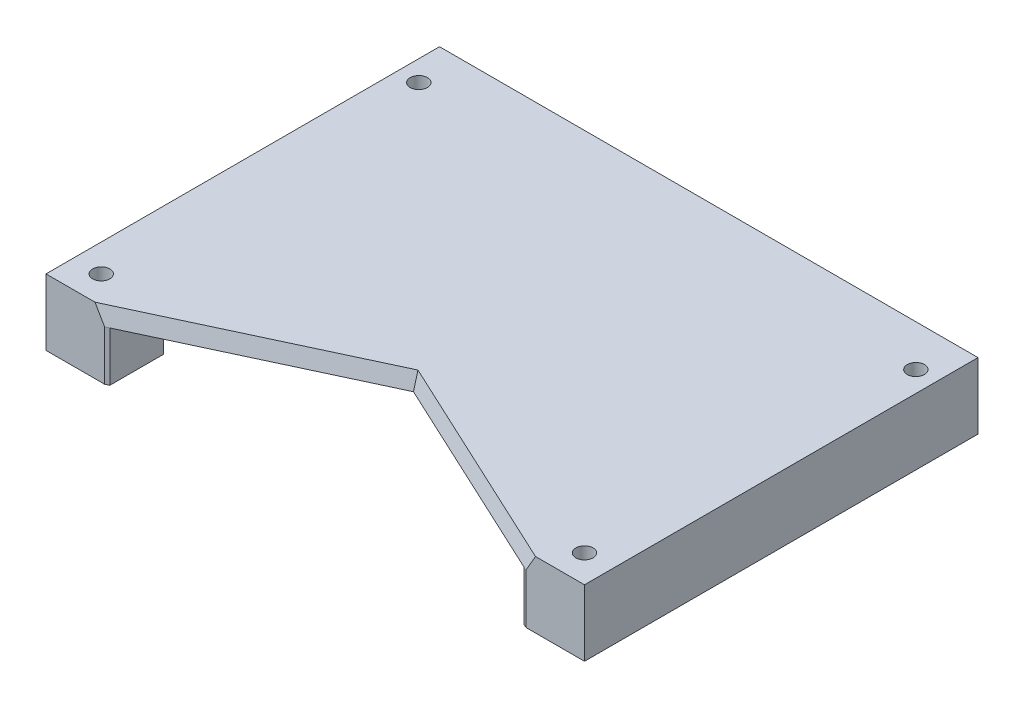
SolidWorks part; units mm, degrees
ref_plane "Front Plane" through (0, 0, 0) normal (0, 0, 1) x (1, 0, 0)
ref_plane "Top Plane" through (0, 0, 0) normal (0, 1, 0) x (1, 0, 0)
ref_plane "Right Plane" through (0, 0, 0) normal (1, 0, 0) x (0, 0, -1)
sketch "Sketch1" plane through (0, 0, 0) normal (0, 1, 0) x (1, 0, 0)
  line L1 (0, 0) -> (78, 0)
  line L2 (0, 0) -> (0, 57)
  line L3 (0, 57) -> (78, 57)
  line L4 (78, 0) -> (78, 57)
  dimension "D1" = 57
  dimension "D2" = 78
extrude "Boss-Extrude1" add sketch "Sketch1" along normal blind 9.6
sketch "Sketch2" plane through (0, 0, 0) normal (0, -1, 0) x (1, 0, 0)
  line L0 (78, -57) -> (0, -57) construction
  line L1 (6, -57) -> (72, -57)
  line L2 (6, -57) -> (6, -8)
  line L3 (6, -8) -> (72, -8)
  line L4 (72, -57) -> (72, -8)
  line L5 (0, -57) -> (0, 0) construction
  line L6 (78, 0) -> (78, -57) construction
  dimension "D1" = 6
  dimension "D2" = 6
  dimension "D3" = 49
extrude "Cut-Extrude1" cut sketch "Sketch2" against normal blind 7.2
sketch "Sketch3" plane through (0, 0, 0) normal (0, -1, 0) x (1, 0, 0)
  line L0 (72, -8) -> (6, -8) construction
  line L1 (9, -8) -> (69, -8)
  line L2 (9, -8) -> (9, 0)
  line L3 (9, 0) -> (69, 0)
  line L4 (69, -8) -> (69, 0)
  line L5 (0, 0) -> (78, 0) construction
  line L6 (0, -57) -> (0, 0) construction
  line L7 (78, 0) -> (78, -57) construction
  dimension "D1" = 9
  dimension "D2" = 9
extrude "Cut-Extrude2" cut sketch "Sketch3" against normal up to surface (7.2 mm away) up to face at (39, 7.2, -32.5)
sketch "Sketch4" plane through (0, 9.6, 0) normal (0, 1, 0) x (1, 0, 0)
  line L0 (0, 0) -> (78, 0) construction
  line L1 (6, 0) -> (39, 15.3882)
  line L2 (39, 15.3882) -> (72, 0)
  line L3 (39, 15.3882) -> (39, 57) construction
  line L4 (72, 0) -> (6, 0)
  line L5 (78, 57) -> (0, 57) construction
  dimension "D1" = 130
  dimension "D2" = 6
extrude "Cut-Extrude3" cut sketch "Sketch4" against normal up to next
hole_wizard "Tap Drill for M3 Tap1" positions "Sketch6" profile "Sketch5" hole size "M3" standard "ISO" end condition up to next
sketch "Sketch6" plane through (0, 0, 0) normal (0, -1, 0) x (-1, 0, 0)
  line L0 (-78, 57) -> (-72, 57) construction
  line L1 (-6, 57) -> (0, 57) construction
  line L2 (-72, 0) -> (-78, 0) construction
  line L3 (-78, 0) -> (-78, 57) construction
  line L5 (0, 57) -> (0, 0) construction
  point P0 (-4, 4)
  point P2 (-3, 51)
  point P4 (-74, 4)
  point P6 (-75, 51)
  dimension "D1" = 6
  dimension "D2" = 6
  dimension "D3" = 4
  dimension "D4" = 4
  dimension "D5" = 4
  dimension "D6" = 3
  dimension "D7" = 3
sketch "Sketch5" plane through (4, 0, -4) normal (1, 0, 0) x (0, 0, -1)
  line L0 (0, 0) -> (0, 9.6)
  line L1 (0, 9.6) -> (1.25, 9.6)
  line L2 (1.25, 9.6) -> (1.25, 0)
  line L5 (1.25, 0) -> (0, 0)
  line L11 (0, -6.35) -> (0, 107.95) construction
  dimension "Thru Hole Dia." = 2.5
  dimension "Thru Hole Depth" = 9.6
ref_plane "Plane1" through (59.1404, 0, 27.5776) normal (0.9063, 0, 0.4226) x (0, 1, 0)
sketch "Sketch7" plane through (0, 9.6, 0) normal (0, 1, 0) x (1, 0, 0)
  line L0 (6, 0) -> (10.7324, 0)
  line L1 (10.7324, 0) -> (39, 13.1814)
  line L2 (39, 13.1814) -> (67.2676, 0)
  line L3 (67.2676, 0) -> (72, 0)
  line L4 (72, 0) -> (39, 15.3882)
  line L5 (39, 15.3882) -> (6, 0)
  dimension "D1" = 2
extrude "Boss-Extrude2" add sketch "Sketch7" against normal up to surface (2.4 mm away) up to face at (39, 7.2, -18.2429)
sketch "Sketch8" plane through (59.1404, 0, 27.5776) normal (0.9063, 0, 0.4226) x (0, 1, 0)
  line L0 (-8, 1.5251) -> (-8, -29.9285) construction
  line L1 (9.6, -29.9285) -> (-8, -29.9285) construction
  line L2 (9.6, -32.9642) -> (9.6, -84.6238) construction
  line L3 (7.2, -9.7862) -> (7.2, -54.1953) construction
  line L4 (9.6, -28.4285) -> (9.6, -32.9642) construction
  line L5 (7.2, -29.378) -> (9.6, -29.9651)
  line L6 (9.6, -29.9651) -> (9.6, -29.7223) construction
  line L7 (7.2, -29.378) -> (7.2, -29.6209) construction
  line L8 (7.2, -29.378) -> (7.2, -29.3415) construction
  line L9 (9.6, -29.9651) -> (9.6, -29.9285) construction
  line L10 (7.2, -30.4285) -> (7.2, -28.4285) construction
  line L11 (9.6, -29.9651) -> (9.6, -28.4285)
  line L12 (9.6, -28.4285) -> (7.2, -28.4285)
  line L13 (7.2, -28.4285) -> (7.2, -29.378)
  circle A0 centre (13.5, -8.7852) radius 21.5 construction
  dimension "D1" = 43
  dimension "D2" = 17.6
  dimension "D3" = 1.5
sketch "Sketch9" plane through (0, 9.6, 0) normal (0, 1, 0) x (1, 0, 0)
  line L0 (72, 0) -> (39, 15.3882)
  line L1 (67.2676, 0) -> (78, 0) construction
  line L2 (39, 15.3882) -> (6, 0)
  line L3 (0, 0) -> (10.7324, 0) construction
  line L4 (10.7324, 0) -> (39, 13.1814) construction
  line L5 (39, 13.1814) -> (67.2676, 0) construction
  dimension "D1" = 2
sweep "Cut-Sweep3" cut profiles "Sketch8" path "Sketch9"
sketch "Sketch11" plane through (0, 7.2, 0) normal (0, -1, 0) x (1, 0, 0)
  line L0 (6, 0) -> (8.4857, 0)
  line L1 (8.4857, 0) -> (9, -0.2398)
  line L2 (39, -14.2291) -> (8.4857, 0) construction
  line L3 (9, -0.2398) -> (9, -1.3989)
  line L4 (9, -1.3989) -> (6, 0)
  line L5 (69, -1.3989) -> (69, -0.2398)
  line L6 (39, -14.2291) -> (69.5143, 0) construction
  line L7 (69, -0.2398) -> (69.5143, 0)
  line L8 (69.5143, 0) -> (72, 0)
  line L9 (59.9098, 25.9276) -> (58.3709, 29.2276) construction
  line L10 (72, 0) -> (69.5143, 0) construction
  line L11 (72, 0) -> (69, -1.3989)
extrude "Boss-Extrude3" add sketch "Sketch11" along normal up to surface (7.2 mm away) up to face at (4, 0, -5.25)
